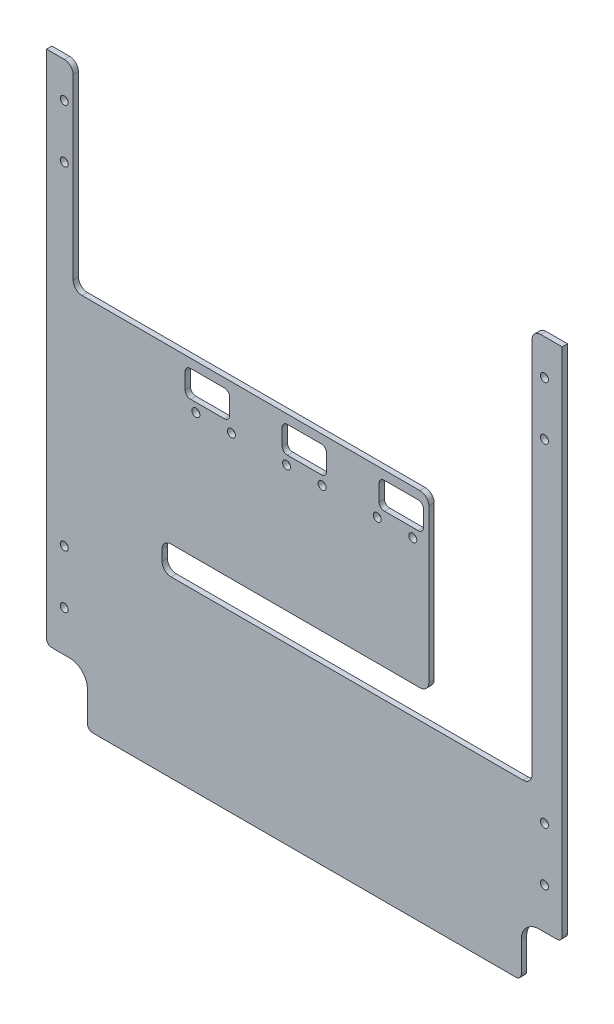
SolidWorks part; units mm, degrees
ref_plane "Front" through (0, 0, 0) normal (0, 0, 1) x (1, 0, 0)
ref_plane "Top" through (0, 0, 0) normal (0, 1, 0) x (1, 0, 0)
ref_plane "Right" through (0, 0, 0) normal (1, 0, 0) x (0, 0, -1)
sketch "Esquisse1" plane through (0, 0, 0) normal (0, 0, 1) x (1, 0, 0)
  line L1 (0, 0) -> (290, 0)
  line L2 (0, 0) -> (0, 320)
  line L3 (0, 320) -> (290, 320)
  line L4 (290, 0) -> (290, 320)
  dimension "D1" = 290
  dimension "D2" = 320
extrude "Boss.-Extru.1" add sketch "Esquisse1" along normal blind 3
sketch "Esquisse2" plane through (0, 0, 3) normal (0, 0, 1) x (1, 0, 0)
  line L0 (145, 0) -> (145, 56.1801) construction
  line L1 (290, 0) -> (267, 0)
  line L2 (290, 0) -> (290, 30)
  line L3 (290, 30) -> (267, 30)
  line L4 (267, 0) -> (267, 30)
  line L5 (0, 0) -> (290, 0) construction
  line L6 (23, 0) -> (23, 30)
  line L7 (0, 30) -> (23, 30)
  line L8 (0, 0) -> (0, 30)
  line L9 (0, 0) -> (23, 0)
  dimension "D1" = 23
  dimension "D2" = 30
extrude "Enlèv. mat.-Extru.1" cut sketch "Esquisse2" against normal through all both and the other way through all
fillet "Congé1" radius 10 2 edges at (267, 30, 1.5) (23, 30, 1.5)
fillet "Congé2" radius 3 4 edges at (290, 30, 1.5) (0, 30, 1.5) (23, 0, 1.5) (267, 0, 1.5)
sketch "Esquisse3" plane through (0, 0, 3) normal (0, 0, 1) x (1, 0, 0)
  line L0 (290, 320) -> (0, 320) construction
  line L1 (75, 320) -> (215, 320)
  line L2 (75, 320) -> (75, 210)
  line L3 (75, 210) -> (215, 210)
  line L4 (215, 320) -> (215, 210)
  line L5 (145, 210) -> (145, 0) construction
  line L6 (26, 0) -> (264, 0) construction
  dimension "D1" = 140
  dimension "D2" = 110
extrude "Enlèv. mat.-Extru.2" cut sketch "Esquisse3" against normal through all both and the other way through all
sketch "Esquisse4" plane through (0, 0, 3) normal (0, 0, 1) x (1, 0, 0)
  line L0 (290, 320) -> (215, 320) construction
  line L1 (215, 320) -> (273, 320)
  line L2 (215, 320) -> (215, 98)
  line L3 (215, 98) -> (273, 98)
  line L4 (273, 320) -> (273, 98)
  line L5 (290, 33) -> (290, 320) construction
  line L6 (215, 320) -> (215, 210) construction
  line L7 (26, 0) -> (264, 0) construction
  dimension "D1" = 17
  dimension "D2" = 98
extrude "Enlèv. mat.-Extru.3" cut sketch "Esquisse4" against normal through all both and the other way through all
sketch "Esquisse5" plane through (0, 0, 3) normal (0, 0, 1) x (1, 0, 0)
  line L0 (75, 320) -> (0, 320) construction
  line L1 (75, 210) -> (15, 210)
  line L2 (75, 210) -> (75, 320)
  line L3 (75, 320) -> (15, 320)
  line L4 (15, 210) -> (15, 320)
  line L5 (0, 320) -> (0, 33) construction
  dimension "D1" = 15
extrude "Enlèv. mat.-Extru.4" cut sketch "Esquisse5" against normal through all both and the other way through all
sketch "Esquisse6" plane through (0, 0, 3) normal (0, 0, 1) x (1, 0, 0)
  line L0 (215, 98) -> (215, 210) construction
  line L1 (215, 98) -> (65, 98)
  line L2 (215, 98) -> (215, 114)
  line L3 (215, 114) -> (65, 114)
  line L4 (65, 98) -> (65, 114)
  line L5 (26, 0) -> (264, 0) construction
  line L6 (0, 320) -> (0, 33) construction
  dimension "D1" = 16
  dimension "D2" = 98
  dimension "D3" = 65
extrude "Enlèv. mat.-Extru.5" cut sketch "Esquisse6" against normal through all both and the other way through all
fillet "Congé3" radius 5 8 edges at (273, 98, 1.5) (65, 98, 1.5) (65, 114, 1.5) (215, 114, 1.5) (215, 210, 1.5) (15, 210, 1.5) (273, 320, 1.5) (15, 320, 1.5)
sketch "Esquisse7" plane through (0, 0, 3) normal (0, 0, 1) x (1, 0, 0)
  line L0 (280, 320) -> (280, 300) construction
  line L1 (290, 320) -> (278, 320) construction
  line L2 (273, 315) -> (273, 103) construction
  line L3 (280, 300) -> (280, 270) construction
  line L4 (145, 0) -> (145, 300) construction
  line L5 (26, 0) -> (264, 0) construction
  line L6 (10, 300) -> (10, 270) construction
  line L7 (10, 320) -> (10, 300) construction
  line L8 (0, 176.5) -> (290, 176.5) construction
  line L9 (0, 320) -> (0, 33) construction
  line L10 (290, 33) -> (290, 320) construction
  line L11 (280, 53) -> (280, 83) construction
  line L12 (280, 33) -> (280, 53) construction
  line L13 (10, 33) -> (10, 53) construction
  line L14 (10, 53) -> (10, 83) construction
  circle A0 centre (280, 300) radius 2.25
  circle A1 centre (280, 270) radius 2.25
  circle A2 centre (10, 270) radius 2.25
  circle A3 centre (10, 300) radius 2.25
  circle A4 centre (280, 83) radius 2.25
  circle A5 centre (280, 53) radius 2.25
  circle A6 centre (10, 53) radius 2.25
  circle A7 centre (10, 83) radius 2.25
  dimension "D2" = 4.5
  dimension "D4" = 30
  dimension "D1" = 7
  dimension "D3" = 20
extrude "Enlèv. mat.-Extru.6" cut sketch "Esquisse7" against normal through all both and the other way through all
sketch "Esquisse8" plane through (0, 0, 3) normal (0, 0, 1) x (1, 0, 0)
  line L0 (145, 0) -> (145, 158.346) construction
  line L1 (26, 0) -> (264, 0) construction
  line L2 (210, 210) -> (20, 210) construction
  line L3 (186, 185) -> (206, 185) construction
  line L4 (155, 185) -> (186, 185) construction
  line L5 (104, 185) -> (84, 185) construction
  circle A0 centre (135, 185) radius 2.25
  circle A1 centre (155, 185) radius 2.25
  circle A2 centre (186, 185) radius 2.25
  circle A3 centre (206, 185) radius 2.25
  circle A4 centre (84, 185) radius 2.25
  circle A5 centre (104, 185) radius 2.25
  dimension "D1" = 4.5
  dimension "D2" = 20
  dimension "D3" = 25
  dimension "D4" = 20
  dimension "D5" = 41
extrude "Enlèv. mat.-Extru.7" cut sketch "Esquisse8" against normal through all both and the other way through all
sketch "Esquisse9" plane through (0, 0, 3) normal (0, 0, 1) x (1, 0, 0)
  line L0 (135, 185) -> (155, 185) construction
  line L1 (132.5, 205) -> (157.5, 205)
  line L2 (132.5, 205) -> (132.5, 190)
  line L3 (132.5, 190) -> (157.5, 190)
  line L4 (157.5, 205) -> (157.5, 190)
  line L5 (145, 185) -> (145, 205) construction
  line L6 (155, 185) -> (172.25, 185) construction
  line L7 (172.25, 185) -> (172.25, 205) construction
  line L8 (187, 205) -> (187, 190)
  line L9 (212, 190) -> (187, 190)
  line L10 (212, 205) -> (212, 190)
  line L11 (212, 205) -> (187, 205)
  line L12 (186, 185) -> (186, 194.1597) construction
  line L13 (104, 185) -> (104, 194.1597) construction
  line L14 (78, 205) -> (103, 205)
  line L15 (78, 205) -> (78, 190)
  line L16 (78, 190) -> (103, 190)
  line L17 (103, 205) -> (103, 190)
  dimension "D1" = 25
  dimension "D2" = 15
  dimension "D3" = 20
  dimension "D4" = 26
extrude "Enlèv. mat.-Extru.8" cut sketch "Esquisse9" against normal through all both and the other way through all
fillet "Congé4" radius 3 12 edges at (157.5, 190, 1.5) (157.5, 205, 1.5) (132.5, 205, 1.5) (132.5, 190, 1.5) (212, 190, 1.5) (212, 205, 1.5) (187, 205, 1.5) (187, 190, 1.5) (103, 190, 1.5) (103, 205, 1.5) (78, 205, 1.5) (78, 190, 1.5)
